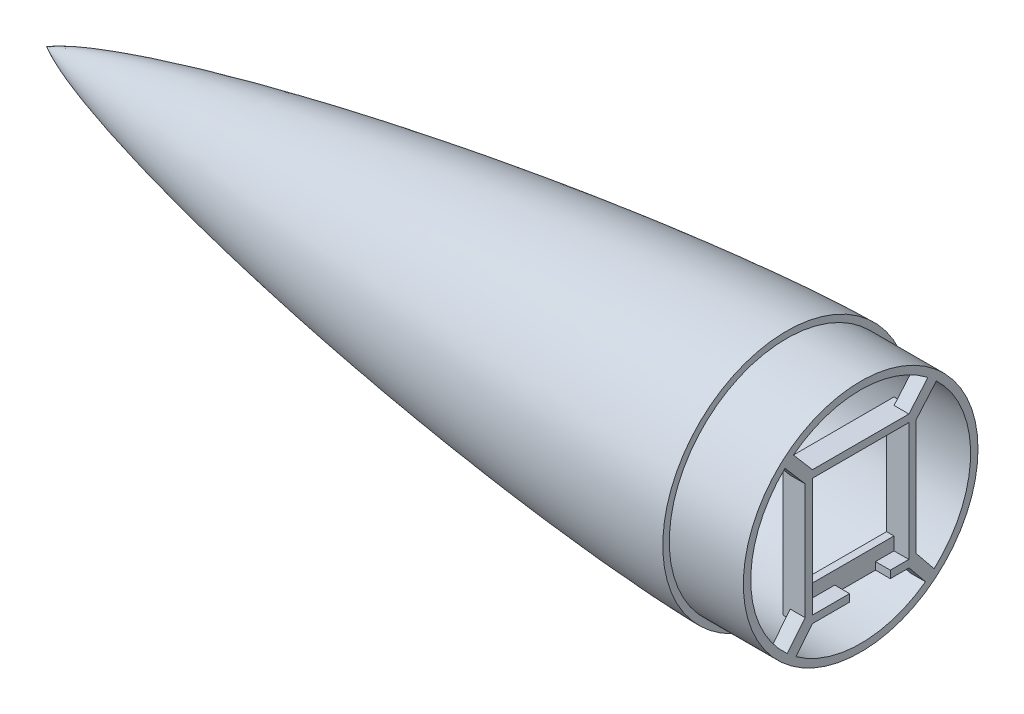
SolidWorks part; units mm, degrees
ref_plane "Front Plane" through (0, 0, 0) normal (0, 0, 1) x (1, 0, 0)
ref_plane "Top Plane" through (0, 0, 0) normal (0, 1, 0) x (1, 0, 0)
ref_plane "Right Plane" through (0, 0, 0) normal (1, 0, 0) x (0, 0, -1)
sketch "Sketch1" plane through (0, 0, 0) normal (0, 1, 0) x (1, 0, 0)
  line L3 (-55, 0) -> (55, 0) construction
  line L4 (200, 33.4356) -> (200, 0)
  line L5 (200, 0) -> (0, 0)
  spline S0 degree 4 poles (0, 0) (0.0297, 0.0027) (0.089, 0.0128) (0.1752, 0.0408) (0.3046, 0.0915) (0.5495, 0.204) (0.9043, 0.3864) (1.5855, 0.7376) (2.7098, 1.2836) (4.4238, 2.0401) (7.065, 3.0857) (10.7984, 4.4109) (16.1615, 6.1222) (23.7399, 8.2919) (33.2254, 10.7239) (44.2444, 13.2746) (56.1293, 15.7818) (68.0528, 18.0982) (80.0071, 20.2486) (91.9875, 22.2489) (103.9905, 24.1086) (116.0136, 25.8328) (128.0552, 27.4233) (140.114, 28.8776) (152.1891, 30.1899) (164.2801, 31.3479) (176.3866, 32.3324) (186.1546, 32.954) (193.5759, 33.2951) (197.9667, 33.411) (199.3222, 33.4323) (200, 33.4356) knots 0 0 0 0 0 0.000585 0.001182 0.001773 0.002733 0.005878 0.009023 0.016834 0.027293 0.042687 0.064838 0.094675 0.13791 0.197585 0.25726 0.316935 0.37661 0.436285 0.495959 0.555634 0.615309 0.674984 0.734659 0.794334 0.854008 0.913683 0.973358 0.986679 1 1 1 1 1 construction
  spline S1 degree 4 poles (0, 0) (0.0297, 0.0027) (0.089, 0.0128) (0.1752, 0.0408) (0.3046, 0.0915) (0.5495, 0.204) (0.9043, 0.3864) (1.5855, 0.7376) (2.7098, 1.2836) (4.4238, 2.0401) (7.065, 3.0857) (10.7984, 4.4109) (16.1615, 6.1222) (23.7399, 8.2919) (33.2254, 10.7239) (44.2444, 13.2746) (56.1293, 15.7818) (68.0528, 18.0982) (80.0071, 20.2486) (91.9875, 22.2489) (103.9905, 24.1086) (116.0136, 25.8328) (128.0552, 27.4233) (140.114, 28.8776) (152.1891, 30.1899) (164.2801, 31.3479) (176.3866, 32.3324) (186.1546, 32.954) (193.5759, 33.2951) (197.9667, 33.411) (199.3222, 33.4323) (200, 33.4356) knots 0 0 0 0 0 0.000585 0.001182 0.001773 0.002733 0.005878 0.009023 0.016834 0.027293 0.042687 0.064838 0.094675 0.13791 0.197585 0.25726 0.316935 0.37661 0.436285 0.495959 0.555634 0.615309 0.674984 0.734659 0.794334 0.854008 0.913683 0.973358 0.986679 1 1 1 1 1
  dimension "D1" = 200
revolve "Cone shape" add sketch "Sketch1" angle 360 about L5
shell "Shell" thickness 1.75 removed face at (200, 0, -33.4356)
sketch "Sketch2" plane through (200, 0, 0) normal (1, 0, 0) x (0, 0, -1)
  circle A0 centre (0, 0) radius 31.6855 construction
  circle A1 centre (0, 0) radius 31.6855
  circle A2 centre (0, 0) radius 29.6855
  dimension "D1" = 2
extrude "Body tube insert" add sketch "Sketch2" against normal up to next and the other way blind 20
ref_plane "GPS plane" through (214, 0, 0) normal (1, 0, 0) x (0, 0, -1)
sketch "Sketch3" plane through (214, 0, 0) normal (1, 0, 0) x (0, 0, -1)
  line L1 (-13, 13) -> (13, 13)
  line L2 (-13, 13) -> (-13, -13)
  line L3 (-13, -13) -> (13, -13)
  line L4 (13, 13) -> (13, -13)
  line L5 (-13, 13) -> (13, -13) construction
  line L6 (-13, -13) -> (13, 13) construction
  line L7 (-15, 17.5) -> (15, 17.5)
  line L8 (-15, 17.5) -> (-15, -18.5)
  line L9 (-15, -18.5) -> (15, -18.5)
  line L10 (15, 17.5) -> (15, -18.5)
  point P0 (0, 0)
  dimension "D1" = 26
  dimension "D2" = 2
  dimension "D3" = 2
  dimension "D4" = 4.5
  dimension "D5" = 5.5
extrude "GPS top" add sketch "Sketch3" along normal blind 2 separate body
sketch "Sketch4" plane through (216, 0, 0) normal (1, 0, 0) x (0, 0, -1)
  line L0 (-13.0689, -18.5) -> (-3, -18.5)
  line L1 (-15, -18.5) -> (15, -18.5) construction
  line L2 (-3, -18.5) -> (-3, -16.5)
  line L3 (-3, -16.5) -> (-13, -16.5)
  line L4 (-15, 17.5) -> (-15, -18.5)
  line L5 (-15, -18.5) -> (15, -18.5)
  line L6 (15, -18.5) -> (15, 17.5)
  line L7 (15, 17.5) -> (-15, 17.5)
  line L8 (-15, 15.1951) -> (-15, -16.1183)
  line L10 (15, -16.1183) -> (15, 15.1951)
  line L11 (13.0244, 17.5) -> (-13.0244, 17.5)
  line L12 (-13, -16.5) -> (-13, 15.5)
  line L13 (-13, 15.5) -> (13, 15.5)
  line L14 (13, 15.5) -> (13, -16.5)
  line L15 (13, -16.5) -> (8, -16.5)
  line L16 (8, -16.5) -> (8, -18.5)
  line L17 (8, -18.5) -> (13.0689, -18.5)
  line L18 (13, -13) -> (13, 13) construction
  line L19 (-13, 13) -> (-13, -13) construction
  line L20 (-15, 17.5) -> (-19.3191, 22.5389) construction
  line L21 (15, 17.5) -> (19.3191, 22.5389) construction
  line L22 (-15, -18.5) -> (-18.696, -23.0584) construction
  line L23 (15, -18.5) -> (18.696, -23.0584) construction
  line L24 (-13.0689, -18.5) -> (-17.507, -23.9737)
  line L25 (-15, -16.1183) -> (-19.8373, -22.0843)
  line L26 (15, -16.1183) -> (19.8373, -22.0843)
  line L27 (13.0689, -18.5) -> (17.507, -23.9737)
  line L28 (13.0244, 17.5) -> (18.1555, 23.4863)
  line L29 (15, 15.1951) -> (20.4333, 21.534)
  line L30 (-13.0244, 17.5) -> (-18.1555, 23.4863)
  line L31 (-15, 15.1951) -> (-20.4333, 21.534)
  circle A0 centre (0, 0) radius 29.6855 construction
  arc A1 (17.507, -23.9737) -> (19.8373, -22.0843) centre (0, 0) ccw
  arc A2 (-19.8373, -22.0843) -> (-17.507, -23.9737) centre (0, 0) ccw
  arc A3 (20.4333, 21.534) -> (18.1555, 23.4863) centre (0, 0) ccw
  arc A4 (-18.1555, 23.4863) -> (-20.4333, 21.534) centre (0, 0) ccw
  dimension "D2" = 11
  dimension "D3" = 5
  dimension "D4" = 2
  dimension "D5" = 2
  dimension "D6" = 1.5
  dimension "D7" = 1.5
  dimension "D8" = 1.5
  dimension "D9" = 1.5
  dimension "D10" = 1.5
  dimension "D11" = 1.5
  dimension "D12" = 1.5
  dimension "D13" = 1.5
  dimension "D1" = 0
extrude "GPS pcb craddle" add sketch "Sketch4" along normal blind 4
